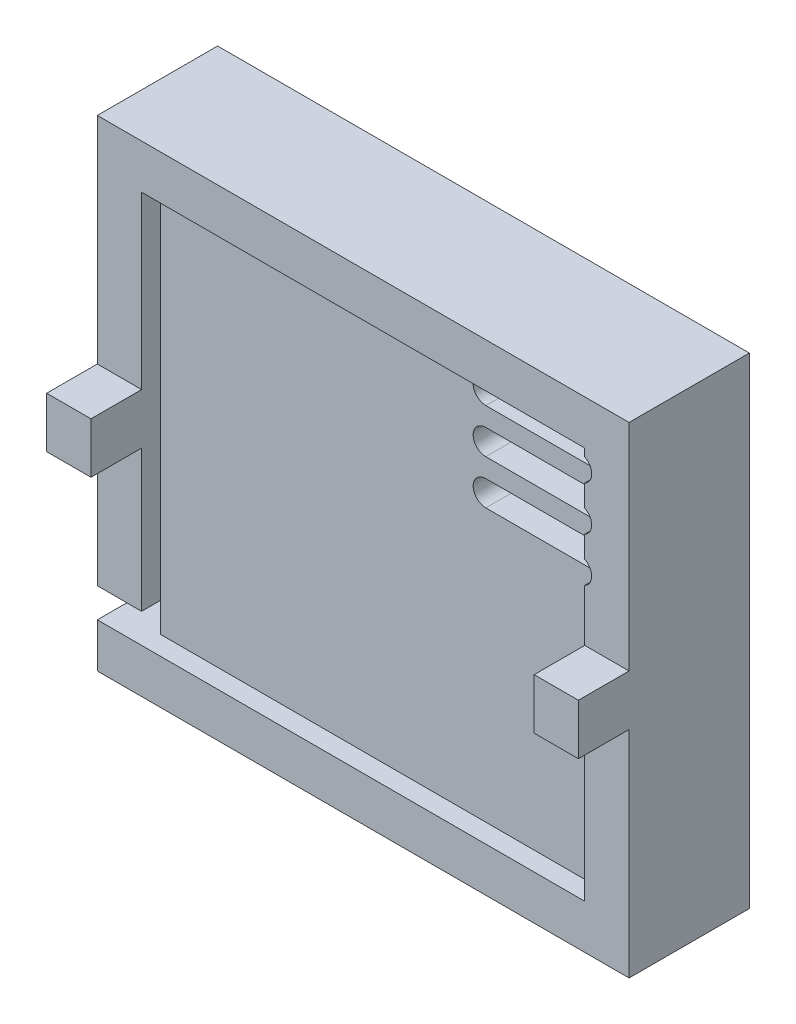
SolidWorks part; units mm, degrees
ref_plane "前视基准面" through (0, 0, 0) normal (0, 0, 1) x (1, 0, 0)
ref_plane "上视基准面" through (0, 0, 0) normal (0, 1, 0) x (1, 0, 0)
ref_plane "右视基准面" through (0, 0, 0) normal (1, 0, 0) x (0, 0, -1)
sketch "草图1" plane through (0, 0, 0) normal (0, 0, 1) x (1, 0, 0)
  line L1 (0, 0) -> (42, 0)
  line L2 (0, 0) -> (0, 38)
  line L3 (0, 38) -> (42, 38)
  line L4 (42, 0) -> (42, 38)
  dimension "D1" = 38
  dimension "D2" = 42
extrude "凸台-拉伸1" add sketch "草图1" along normal blind 3.5
sketch "草图2" plane through (0, 0, 3.5) normal (0, 0, 1) x (1, 0, 0)
  line L0 (0, 19) -> (0, 21)
  line L1 (0, 38) -> (0, 0) construction
  line L2 (42, 19) -> (42, 21)
  line L3 (0, 21) -> (3.5, 21)
  line L4 (0, 21) -> (0, 17)
  line L5 (0, 17) -> (3.5, 17)
  line L6 (3.5, 21) -> (3.5, 17)
  line L7 (42, 0) -> (42, 38) construction
  line L9 (42, 21) -> (38.5, 21)
  line L10 (42, 21) -> (42, 17)
  line L11 (42, 17) -> (38.5, 17)
  line L12 (38.5, 21) -> (38.5, 17)
  point P14 (0, 0)
  line M7 (0, 38) -> (0, 0)
  line M9 (42, 0) -> (42, 38)
  dimension "D1" = 2
  dimension "D2" = 3.5
  dimension "D3" = 4
  dimension "D4" = 2
  dimension "D5" = 4
  dimension "D6" = 3.5
extrude "凸台-拉伸2" add sketch "草图2" along normal blind 4 contours L6 L3 L5 M7 | L9 L12 L11 M9 region at (1.75, 19, 3.5) region at (40.25, 19, 3.5)
sketch "草图3" plane through (0, 0, 3.5) normal (0, 0, 1) x (1, 0, 0)
  line L1 (0, 0) -> (3.5, 0) construction
  line L2 (0, 0) -> (0, 3.5) construction
  line L3 (0, 3.5) -> (3.5, 3.5) construction
  line L4 (3.5, 0) -> (3.5, 3.5) construction
  line L5 (3.5, 3.5) -> (38.5, 3.5)
  line L6 (3.5, 3.5) -> (3.5, 34.5)
  line L7 (3.5, 34.5) -> (38.5, 34.5)
  line L8 (38.5, 3.5) -> (38.5, 34.5)
  dimension "D1" = 3.5
  dimension "D2" = 3.5
  dimension "D3" = 31
  dimension "D4" = 35
extrude "切除-拉伸1" cut sketch "草图3" against normal blind 1.5
sketch "草图4" plane through (0, 0, 0) normal (0, 0, -1) x (-1, 0, 0)
  line L0 (-42, 38) -> (0, 38) construction
  line L1 (-42, 0) -> (-38.5, 0) construction
  line L2 (-42, 0) -> (-42, 3.5) construction
  line L3 (-42, 3.5) -> (-38.5, 3.5) construction
  line L4 (-38.5, 0) -> (-38.5, 3.5) construction
  line L5 (-38.5, 3.5) -> (-3.5, 3.5)
  line L6 (-38.5, 3.5) -> (-38.5, 34.5)
  line L7 (-38.5, 34.5) -> (-3.5, 34.5)
  line L8 (-3.5, 3.5) -> (-3.5, 34.5)
  line L9 (-42, 0) -> (0, 0)
  line L10 (-42, 0) -> (-42, 38)
  line L11 (-42, 38) -> (0, 38)
  line L12 (0, 0) -> (0, 38)
  dimension "D1" = 3.5
  dimension "D2" = 3.5
  dimension "D3" = 31
  dimension "D4" = 35
extrude "凸台-拉伸3" add sketch "草图4" along normal blind 4 contours L10 L9 L12 L11 | L6 L5 L8 L7
sketch "草图6" plane through (0, 0, -4) normal (0, 0, -1) x (-1, 0, 0)
  line L1 (-42, 38) -> (0, 38)
  line L2 (-42, 38) -> (-42, 0)
  line L3 (-42, 0) -> (0, 0)
  line L4 (0, 38) -> (0, 0)
extrude "凸台-拉伸4" add sketch "草图6" along normal blind 2
sketch "草图7" plane through (0, 0, 0) normal (-1, 0, 0) x (0, 0, 1)
  line L1 (3.5, 0) -> (0, 0) construction
  line L2 (3.5, 0) -> (3.5, 3.5) construction
  line L3 (3.5, 3.5) -> (0, 3.5) construction
  line L4 (0, 0) -> (0, 3.5) construction
  line L5 (0, 3.5) -> (-4, 3.5)
  line L6 (0, 3.5) -> (0, 28.5)
  line L7 (0, 28.5) -> (-4, 28.5)
  line L8 (-4, 3.5) -> (-4, 28.5)
  dimension "D1" = 3.5
  dimension "D2" = 3.5
  dimension "D3" = 4
  dimension "D4" = 25
extrude "切除-拉伸2" cut sketch "草图7" against normal blind 3.5
sketch "草图8" plane through (0, 0, 0) normal (-1, 0, 0) x (0, 0, 1)
  line L0 (3.5, 17) -> (3.5, 0) construction
  line L1 (0, 3.5) -> (3.5, 3.5)
  line L2 (0, 3.5) -> (0, 5.8318)
  line L3 (0, 5.8318) -> (3.5, 5.8318)
  line L4 (3.5, 3.5) -> (3.5, 5.8318)
extrude "切除-拉伸3" cut sketch "草图8" against normal blind 3.5
sketch "草图9" plane through (0, 0, -6) normal (0, 0, -1) x (-1, 0, 0)
  line L0 (-38.0447, 26) -> (-29.1868, 26) construction
  line L1 (-42, 0) -> (-38.5, 0) construction
  line L2 (-42, 0) -> (-42, 3.5) construction
  line L3 (-42, 3.5) -> (-38.5, 3.5) construction
  line L4 (-38.5, 0) -> (-38.5, 3.5) construction
  line L5 (-38.5, 3.5) -> (-28.5, 3.5) construction
  line L6 (-38.5, 3.5) -> (-38.5, 15.5) construction
  line L7 (-38.5, 15.5) -> (-28.5, 15.5) construction
  line L8 (-28.5, 3.5) -> (-28.5, 15.5) construction
  line L9 (-38.0447, 27) -> (-29.1868, 27)
  line L10 (-38.0447, 25) -> (-29.1868, 25)
  line L11 (-38.0447, 29.5) -> (-29.1868, 29.5) construction
  line L12 (-38.0447, 30.5) -> (-29.1868, 30.5)
  line L13 (-38.0447, 28.5) -> (-29.1868, 28.5)
  line L14 (-38.0447, 33) -> (-29.1868, 33) construction
  line L15 (-38.0447, 34) -> (-29.1868, 34)
  line L16 (-38.0447, 32) -> (-29.1868, 32)
  arc A0 (-38.0447, 27) -> (-38.0447, 25) centre (-38.0447, 26) ccw
  arc A1 (-29.1868, 25) -> (-29.1868, 27) centre (-29.1868, 26) ccw
  arc A2 (-38.0447, 30.5) -> (-38.0447, 28.5) centre (-38.0447, 29.5) ccw
  arc A3 (-29.1868, 28.5) -> (-29.1868, 30.5) centre (-29.1868, 29.5) ccw
  arc A4 (-38.0447, 34) -> (-38.0447, 32) centre (-38.0447, 33) ccw
  arc A5 (-29.1868, 32) -> (-29.1868, 34) centre (-29.1868, 33) ccw
  point P10 (-33.6157, 26)
  point P15 (-33.6157, 29.5)
  point P22 (-33.6157, 33)
  dimension "D5" = 1
  dimension "D6" = 1
  dimension "D7" = 1
  dimension "D1" = 3.5
  dimension "D2" = 3.5
  dimension "D3" = 10
  dimension "D4" = 12
extrude "切除-拉伸4" cut sketch "草图9" against normal blind 10 contours L16 A5 L15 A4 | L13 A3 L12 A2 | L10 A1 L9 A0
sketch "草图10" plane through (0, 0, 0) normal (0, 0, -1) x (-1, 0, 0)
  line L3 (-27.9839, 34.5) -> (-26.1454, 34.5)
  line L6 (-27.9839, 34.5) -> (-26.4839, 34.5)
  line L7 (-27.9839, 34.5) -> (-27.9839, 3.5)
  line L8 (-27.9839, 3.5) -> (-26.4839, 3.5)
  line L9 (-26.4839, 34.5) -> (-26.4839, 3.5)
  line L10 (-27.9839, 3.5) -> (-26.1454, 3.5)
  point P0 (0, 0)
  line M22 (-38.5, 3.5) -> (-3.5, 3.5)
  dimension "D2" = 1.5
extrude "凸台-拉伸5" add sketch "草图10" along normal blind 5 contours L9 L3 L7 M22 region at (27.2339, 19, 0)
